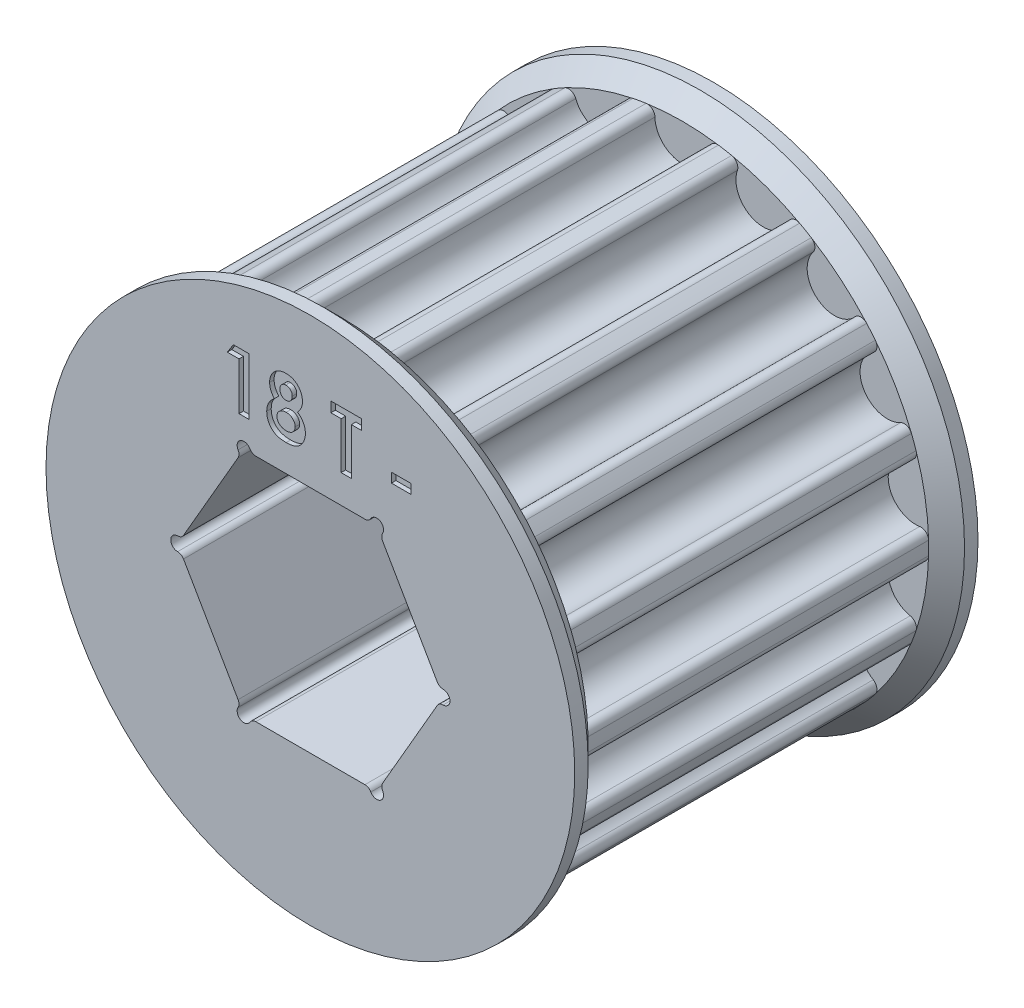
SolidWorks part; units mm, degrees
material "Nailon 6/10"
ref_plane "Alzado" through (0, 0, 0) normal (0, 0, 1) x (1, 0, 0)
ref_plane "Planta" through (0, 0, 0) normal (0, 1, 0) x (1, 0, 0)
ref_plane "Vista lateral" through (0, 0, 0) normal (1, 0, 0) x (0, 0, -1)
sketch "Croquis3" plane through (0, 0, 0) normal (0, 0, 1) x (1, 0, 0)
  line L0 (0, 0) -> (0, 13.75) construction
  line L1 (0, 0) -> (4.7028, 12.9208) construction
  circle A0 centre (0, 0) radius 13.75 construction
  circle A1 centre (0, 0) radius 11.69 construction
  circle A2 centre (0, 13.215) radius 1.525 construction
  circle A3 centre (1.9546, 13.1758) radius 0.43 construction
  circle A4 centre (4.5198, 12.418) radius 1.525 construction
  circle A5 centre (2.6697, 13.0497) radius 0.43 construction
  arc A6 (0, 11.69) -> (1.5247, 13.1844) centre (0, 13.215) ccw
  arc A7 (1.5247, 13.1844) -> (2.0177, 13.6012) centre (1.9546, 13.1758) cw
  arc A8 (2.0177, 13.6012) -> (2.7558, 13.471) centre (0, 0) cw
  arc A9 (2.7558, 13.471) -> (3.0766, 12.9108) centre (2.6697, 13.0497) cw
  arc A10 (3.0766, 12.9108) -> (3.9982, 10.985) centre (4.5198, 12.418) ccw
  arc A11 (7.3068, 11.0799) -> (7.5142, 8.9551) centre (8.4944, 10.1233) ccw
  arc A12 (7.197, 11.716) -> (7.3068, 11.0799) centre (6.9719, 11.3497) cw
  arc A13 (6.5479, 12.0908) -> (7.197, 11.716) centre (0, 0) cw
  arc A14 (5.9421, 11.8678) -> (6.5479, 12.0908) centre (6.3431, 11.7127) cw
  arc A15 (3.9982, 10.985) -> (5.9421, 11.8678) centre (4.5198, 12.418) ccw
  arc A16 (10.6557, 7.9126) -> (10.1238, 5.845) centre (11.4445, 6.6075) ccw
  arc A17 (10.7701, 8.548) -> (10.6557, 7.9126) centre (10.4333, 8.2806) cw
  arc A18 (10.2883, 9.1221) -> (10.7701, 8.548) centre (0, 0) cw
  arc A19 (9.6428, 9.1198) -> (10.2883, 9.1221) centre (9.9666, 8.8369) cw
  arc A20 (7.5142, 8.9551) -> (9.6428, 9.1198) centre (8.4944, 10.1233) ccw
  arc A21 (12.7194, 3.791) -> (11.5124, 2.0299) centre (13.0142, 2.2948) ccw
  arc A22 (13.0441, 4.3489) -> (12.7194, 3.791) centre (12.6362, 4.2129) cw
  arc A23 (12.7878, 5.0532) -> (13.0441, 4.3489) centre (0, 0) cw
  arc A24 (12.1804, 5.2718) -> (12.7878, 5.0532) centre (12.3879, 4.8952) cw
  arc A25 (10.1238, 5.845) -> (12.1804, 5.2718) centre (11.4445, 6.6075) ccw
  arc A26 (13.2489, -0.7879) -> (11.5124, -2.0299) centre (13.0142, -2.2948) ccw
  arc A27 (13.7449, -0.3748) -> (13.2489, -0.7879) centre (13.3151, -0.363) cw
  arc A28 (13.7449, 0.3748) -> (13.7449, -0.3748) centre (0, 0) cw
  arc A29 (13.2489, 0.7879) -> (13.7449, 0.3748) centre (13.3151, 0.363) cw
  arc A30 (11.5124, 2.0299) -> (13.2489, 0.7879) centre (13.0142, 2.2948) ccw
  arc A31 (12.1804, -5.2718) -> (10.1238, -5.845) centre (11.4445, -6.6075) ccw
  arc A32 (12.7878, -5.0532) -> (12.1804, -5.2718) centre (12.3879, -4.8952) cw
  arc A33 (13.0441, -4.3489) -> (12.7878, -5.0532) centre (0, 0) cw
  arc A34 (12.7194, -3.791) -> (13.0441, -4.3489) centre (12.6362, -4.2129) cw
  arc A35 (11.5124, -2.0299) -> (12.7194, -3.791) centre (13.0142, -2.2948) ccw
  arc A36 (9.6428, -9.1198) -> (7.5142, -8.9551) centre (8.4944, -10.1233) ccw
  arc A37 (10.2883, -9.1221) -> (9.6428, -9.1198) centre (9.9666, -8.8369) cw
  arc A38 (10.7701, -8.548) -> (10.2883, -9.1221) centre (0, 0) cw
  arc A39 (10.6557, -7.9126) -> (10.7701, -8.548) centre (10.4333, -8.2806) cw
  arc A40 (10.1238, -5.845) -> (10.6557, -7.9126) centre (11.4445, -6.6075) ccw
  arc A41 (5.9421, -11.8678) -> (3.9982, -10.985) centre (4.5198, -12.418) ccw
  arc A42 (6.5479, -12.0908) -> (5.9421, -11.8678) centre (6.3431, -11.7127) cw
  arc A43 (7.197, -11.716) -> (6.5479, -12.0908) centre (0, 0) cw
  arc A44 (7.3068, -11.0799) -> (7.197, -11.716) centre (6.9719, -11.3497) cw
  arc A45 (7.5142, -8.9551) -> (7.3068, -11.0799) centre (8.4944, -10.1233) ccw
  arc A46 (1.5247, -13.1844) -> (0, -11.69) centre (0, -13.215) ccw
  arc A47 (2.0177, -13.6012) -> (1.5247, -13.1844) centre (1.9546, -13.1758) cw
  arc A48 (2.7558, -13.471) -> (2.0177, -13.6012) centre (0, 0) cw
  arc A49 (3.0766, -12.9108) -> (2.7558, -13.471) centre (2.6697, -13.0497) cw
  arc A50 (3.9982, -10.985) -> (3.0766, -12.9108) centre (4.5198, -12.418) ccw
  arc A51 (-3.0766, -12.9108) -> (-3.9982, -10.985) centre (-4.5198, -12.418) ccw
  arc A52 (-2.7558, -13.471) -> (-3.0766, -12.9108) centre (-2.6697, -13.0497) cw
  arc A53 (-2.0177, -13.6012) -> (-2.7558, -13.471) centre (0, 0) cw
  arc A54 (-1.5247, -13.1844) -> (-2.0177, -13.6012) centre (-1.9546, -13.1758) cw
  arc A55 (0, -11.69) -> (-1.5247, -13.1844) centre (0, -13.215) ccw
  arc A56 (-7.3068, -11.0799) -> (-7.5142, -8.9551) centre (-8.4944, -10.1233) ccw
  arc A57 (-7.197, -11.716) -> (-7.3068, -11.0799) centre (-6.9719, -11.3497) cw
  arc A58 (-6.5479, -12.0908) -> (-7.197, -11.716) centre (0, 0) cw
  arc A59 (-5.9421, -11.8678) -> (-6.5479, -12.0908) centre (-6.3431, -11.7127) cw
  arc A60 (-3.9982, -10.985) -> (-5.9421, -11.8678) centre (-4.5198, -12.418) ccw
  arc A61 (-10.6557, -7.9126) -> (-10.1238, -5.845) centre (-11.4445, -6.6075) ccw
  arc A62 (-10.7701, -8.548) -> (-10.6557, -7.9126) centre (-10.4333, -8.2806) cw
  arc A63 (-10.2883, -9.1221) -> (-10.7701, -8.548) centre (0, 0) cw
  arc A64 (-9.6428, -9.1198) -> (-10.2883, -9.1221) centre (-9.9666, -8.8369) cw
  arc A65 (-7.5142, -8.9551) -> (-9.6428, -9.1198) centre (-8.4944, -10.1233) ccw
  arc A66 (-12.7194, -3.791) -> (-11.5124, -2.0299) centre (-13.0142, -2.2948) ccw
  arc A67 (-13.0441, -4.3489) -> (-12.7194, -3.791) centre (-12.6362, -4.2129) cw
  arc A68 (-12.7878, -5.0532) -> (-13.0441, -4.3489) centre (0, 0) cw
  arc A69 (-12.1804, -5.2718) -> (-12.7878, -5.0532) centre (-12.3879, -4.8952) cw
  arc A70 (-10.1238, -5.845) -> (-12.1804, -5.2718) centre (-11.4445, -6.6075) ccw
  arc A71 (-13.2489, 0.7879) -> (-11.5124, 2.0299) centre (-13.0142, 2.2948) ccw
  arc A72 (-13.7449, 0.3748) -> (-13.2489, 0.7879) centre (-13.3151, 0.363) cw
  arc A73 (-13.7449, -0.3748) -> (-13.7449, 0.3748) centre (0, 0) cw
  arc A74 (-13.2489, -0.7879) -> (-13.7449, -0.3748) centre (-13.3151, -0.363) cw
  arc A75 (-11.5124, -2.0299) -> (-13.2489, -0.7879) centre (-13.0142, -2.2948) ccw
  arc A76 (-12.1804, 5.2718) -> (-10.1238, 5.845) centre (-11.4445, 6.6075) ccw
  arc A77 (-12.7878, 5.0532) -> (-12.1804, 5.2718) centre (-12.3879, 4.8952) cw
  arc A78 (-13.0441, 4.3489) -> (-12.7878, 5.0532) centre (0, 0) cw
  arc A79 (-12.7194, 3.791) -> (-13.0441, 4.3489) centre (-12.6362, 4.2129) cw
  arc A80 (-11.5124, 2.0299) -> (-12.7194, 3.791) centre (-13.0142, 2.2948) ccw
  arc A81 (-9.6428, 9.1198) -> (-7.5142, 8.9551) centre (-8.4944, 10.1233) ccw
  arc A82 (-10.2883, 9.1221) -> (-9.6428, 9.1198) centre (-9.9666, 8.8369) cw
  arc A83 (-10.7701, 8.548) -> (-10.2883, 9.1221) centre (0, 0) cw
  arc A84 (-10.6557, 7.9126) -> (-10.7701, 8.548) centre (-10.4333, 8.2806) cw
  arc A85 (-10.1238, 5.845) -> (-10.6557, 7.9126) centre (-11.4445, 6.6075) ccw
  arc A86 (-5.9421, 11.8678) -> (-3.9982, 10.985) centre (-4.5198, 12.418) ccw
  arc A87 (-6.5479, 12.0908) -> (-5.9421, 11.8678) centre (-6.3431, 11.7127) cw
  arc A88 (-7.197, 11.716) -> (-6.5479, 12.0908) centre (0, 0) cw
  arc A89 (-7.3068, 11.0799) -> (-7.197, 11.716) centre (-6.9719, 11.3497) cw
  arc A90 (-7.5142, 8.9551) -> (-7.3068, 11.0799) centre (-8.4944, 10.1233) ccw
  arc A91 (-1.5247, 13.1844) -> (0, 11.69) centre (0, 13.215) ccw
  arc A92 (-2.0177, 13.6012) -> (-1.5247, 13.1844) centre (-1.9546, 13.1758) cw
  arc A93 (-2.7558, 13.471) -> (-2.0177, 13.6012) centre (0, 0) cw
  arc A94 (-3.0766, 12.9108) -> (-2.7558, 13.471) centre (-2.6697, 13.0497) cw
  arc A95 (-3.9982, 10.985) -> (-3.0766, 12.9108) centre (-4.5198, 12.418) ccw
  dimension "D1" = 27.5
  dimension "D2" = 23.38
  dimension "D3" = 3.05
  dimension "D4" = 0.86
  dimension "D5" = 20
  dimension "D6" = 18
extrude "Saliente-Extruir1" add sketch "Croquis3" along normal mid plane 19 contours A65 A56 A57 A58 A59 A60 A51 A52 A53 A54 A55 A46 A47 A48 A49 A50 A41 A42 A43 A44 A45 A36 A37 A38 A39 A40 A31 A32 A33 A34 A35 A26 A27 A28 A29 A30 A21 A22 A23 A24 A25 A16 A17 A18 A19 A20 A11 A12 A13 A14 A15 region at (0, 0, 0)
sketch "Croquis5" plane through (0, 0, 9.5) normal (0, 0, 1) x (1, 0, 0)
  circle A0 centre (0, 0) radius 13.75
  arc A1 (2.7558, 13.471) -> (2.0177, 13.6012) centre (0, 0) ccw construction
extrude "Saliente-Extruir2" add sketch "Croquis5" along normal blind 1 draft 45 draft outward yes
sketch "Croquis7" plane through (0, 0, 10.5) normal (0, 0, 1) x (1, 0, 0)
  circle A0 centre (0, 0) radius 14.75 construction
  circle A1 centre (0, 0) radius 14.75
extrude "Saliente-Extruir3" add sketch "Croquis7" along normal blind 0.75
mirror "Simetría1" about plane through (0, 0, 0) normal (0, 0, 1) of "Saliente-Extruir3", "Saliente-Extruir2"
sketch "Croquis6" plane through (0, 0, 11.25) normal (0, 0, 1) x (1, 0, 0)
  line L5 (3.7037, -6.415) -> (7.4074, 0)
  line L6 (7.4074, 0) -> (3.7037, 6.415)
  line L7 (3.7037, 6.415) -> (-3.7037, 6.415)
  line L8 (-3.7037, 6.415) -> (-7.4074, 0)
  line L9 (-7.4074, 0) -> (-3.7037, -6.415)
  line L10 (-3.7037, -6.415) -> (3.7037, -6.415)
  circle A1 centre (0, 0) radius 6.415 construction
  arc A2 (-3.3227, 6.415) -> (-3.8942, 6.085) centre (-3.7037, 6.415) ccw
  arc A3 (3.8942, 6.085) -> (3.3227, 6.415) centre (3.7037, 6.415) ccw
  arc A4 (7.2169, -0.33) -> (7.2169, 0.33) centre (7.4074, 0) ccw
  arc A5 (3.3227, -6.415) -> (3.8942, -6.085) centre (3.7037, -6.415) ccw
  arc A6 (-3.8942, -6.085) -> (-3.3227, -6.415) centre (-3.7037, -6.415) ccw
  arc A7 (-7.2169, 0.33) -> (-7.2169, -0.33) centre (-7.4074, 0) ccw
  dimension "D1" = 12.83
  dimension "D2" = 0.381
  dimension "D3" = 6
extrude "Cortar-Extruir1" cut sketch "Croquis6" against normal through all contours L9 L10 L5 L6 L7 L8 | L7 A2 L8 | L6 A3 L7 | L5 A4 L6 | L10 A5 L5 | L9 A6 L10 | L8 A7 L9 region at (0, 0, 11.25) region at (3.7562, -6.506, 11.25) region at (7.5124, 0, 11.25) region at (-3.7562, -6.506, 11.25) region at (3.7562, 6.506, 11.25) region at (-7.5124, 0, 11.25) region at (-3.7562, 6.506, 11.25)
fillet "Redondeo1" radius 0.381 12 edges at (-7.2169, 0.33, 0) (3.3227, -6.415, 0) (-3.3227, -6.415, 0) (-7.2169, -0.33, 0) (-3.8942, -6.085, 0) (7.2169, -0.33, 0) (3.8942, -6.085, 0) (7.2169, 0.33, 0) (3.8942, 6.085, 0) (3.3227, 6.415, 0) (-3.8942, 6.085, 0) (-3.3227, 6.415, 0)
sketch "Croquis9" plane through (0, 0, 0) normal (0, 0, 1) x (1, 0, 0)
  line L0 (-5, 8) -> (5, 8) construction
  text T0 "18 T - 15mm" font "Century Gothic" height 3.175
  point P2 (0, 8)
  dimension "D1" = 10
  dimension "D2" = 8
extrude "Cortar-Extruir3" cut sketch "Croquis9" against normal blind 0.25 from surface starting at face at (0, 0, 11.25)
equation "\"X\"=27.5"
equation "\"N\"=18"
equation "\"D1@Croquis3\"=\"X\""
equation "\"Y\"= \"X\" - 2 * 2.06"
equation "\"A\"= 360 / \"N\""
equation "\"D2@Croquis3\"=\"Y\""
equation "\"D5@Croquis3\"=\"A\""
equation "\"D6@Croquis3\"=\"N\""
equation "\"Grosor\" = 19"
equation "\"D1@Saliente-Extruir1\"=\"Grosor\""
